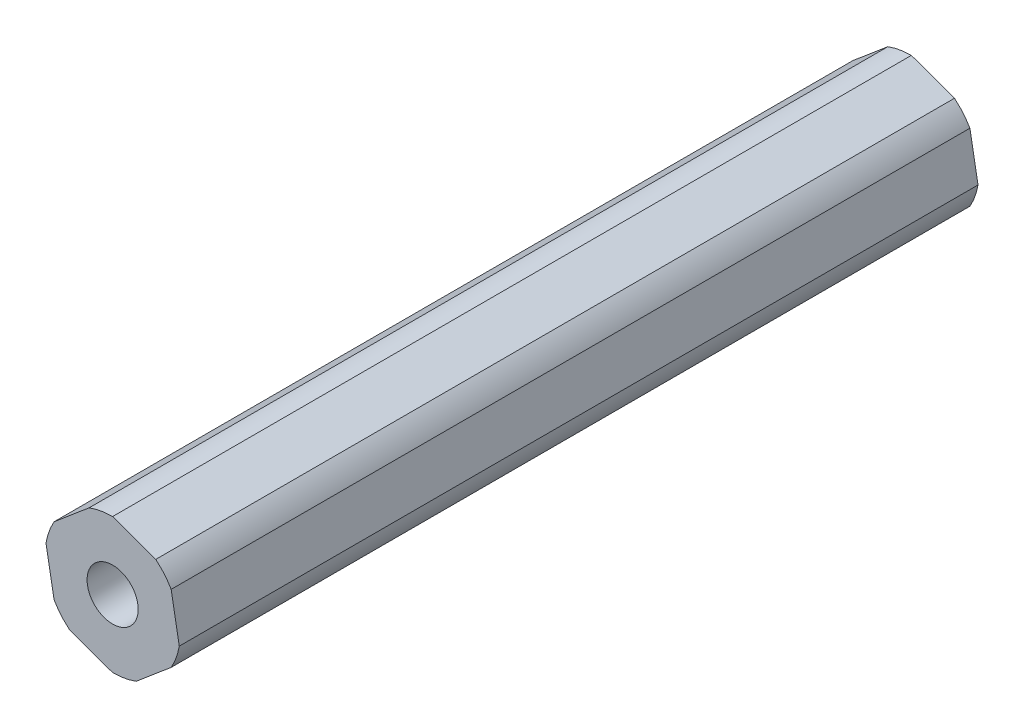
SolidWorks part; units mm, degrees
material "7075-T6 (SN)"
ref_plane "Front Plane" through (0, 0, 0) normal (0, 0, 1) x (1, 0, 0)
ref_plane "Top Plane" through (0, 0, 0) normal (0, 1, 0) x (1, 0, 0)
ref_plane "Right Plane" through (0, 0, 0) normal (1, 0, 0) x (0, 0, -1)
sketch "Sketch1" plane through (0, 0, 0) normal (0, 0, 1) x (1, 0, 0)
  line L1 (-6.6545, 1.1312) -> (-5.8457, -3.375)
  line L2 (-4.3069, -5.1974) -> (0, -6.75)
  line L3 (2.3476, -6.3286) -> (5.8457, -3.375)
  line L4 (6.6545, -1.1312) -> (5.8457, 3.375)
  line L5 (4.3069, 5.1974) -> (0, 6.75)
  line L6 (-2.3476, 6.3286) -> (-5.8457, 3.375)
  circle A0 centre (0, 0) radius 6.35 construction
  arc A1 (-5.8457, 3.375) -> (-6.6545, 1.1312) centre (0, 0) ccw
  arc A2 (-5.8457, -3.375) -> (-4.3069, -5.1974) centre (0, 0) ccw
  arc A3 (0, -6.75) -> (2.3476, -6.3286) centre (0, 0) ccw
  arc A4 (5.8457, -3.375) -> (6.6545, -1.1312) centre (0, 0) ccw
  arc A5 (5.8457, 3.375) -> (4.3069, 5.1974) centre (0, 0) ccw
  arc A6 (0, 6.75) -> (-2.3476, 6.3286) centre (0, 0) ccw
  dimension "D1" = 12.7
  dimension "D2" = 13.5
extrude "Boss-Extrude1" add sketch "Sketch1" along normal blind 79.756
sketch "Sketch2" plane through (0, 0, 79.756) normal (0, 0, 1) x (1, 0, 0)
  circle A0 centre (0, 0) radius 2.0193
  dimension "D1" = 4.0386
extrude "Cut-Extrude1" cut sketch "Sketch2" against normal through all
hole_wizard "1/4-20 Tapped Hole1" positions "Sketch5" profile "Sketch6" tap size "1/4-20" standard "ANSI Inch"
sketch "Sketch5" plane through (0, 0, 79.756) normal (0, 0, 1) x (1, 0, 0)
  point P0 (0, 0)
sketch "Sketch6" plane through (0, 0, 79.756) normal (1, 0, 0) x (0, -1, 0)
  line L0 (0, 0) -> (0, 20.5838)
  line L1 (0, 20.5838) -> (2.5527, 19.05)
  line L2 (2.5527, 19.05) -> (2.5527, 0)
  line L5 (2.5527, 0) -> (0, 0)
  line L10 (0, 20.5838) -> (-2.5527, 19.05) construction
  line L11 (0, -6.35) -> (0, 107.95) construction
  dimension "Tap Drill Dia." = 5.1054
  dimension "Tap Drill Depth" = 19.05
  dimension "Drill Angle" = 118
cosmetic thread "Hole Thread1" parameters "D1"=12.7, "D2"=6.35
hole_wizard "1/4-20 Tapped Hole2" positions "Sketch7" profile "Sketch8" tap size "1/4-20" standard "ANSI Inch"
sketch "Sketch7" plane through (0, 0, 0) normal (0, 0, -1) x (-1, 0, 0)
  point P0 (0, 0)
sketch "Sketch8" plane through (0, 0, 0) normal (1, 0, 0) x (0, 1, 0)
  line L0 (0, 0) -> (0, 20.5838)
  line L1 (0, 20.5838) -> (2.5527, 19.05)
  line L2 (2.5527, 19.05) -> (2.5527, 0)
  line L5 (2.5527, 0) -> (0, 0)
  line L10 (0, 20.5838) -> (-2.5527, 19.05) construction
  line L11 (0, -6.35) -> (0, 107.95) construction
  dimension "Tap Drill Dia." = 5.1054
  dimension "Tap Drill Depth" = 19.05
  dimension "Drill Angle" = 118
cosmetic thread "Hole Thread2" parameters "D1"=12.7, "D2"=6.35
